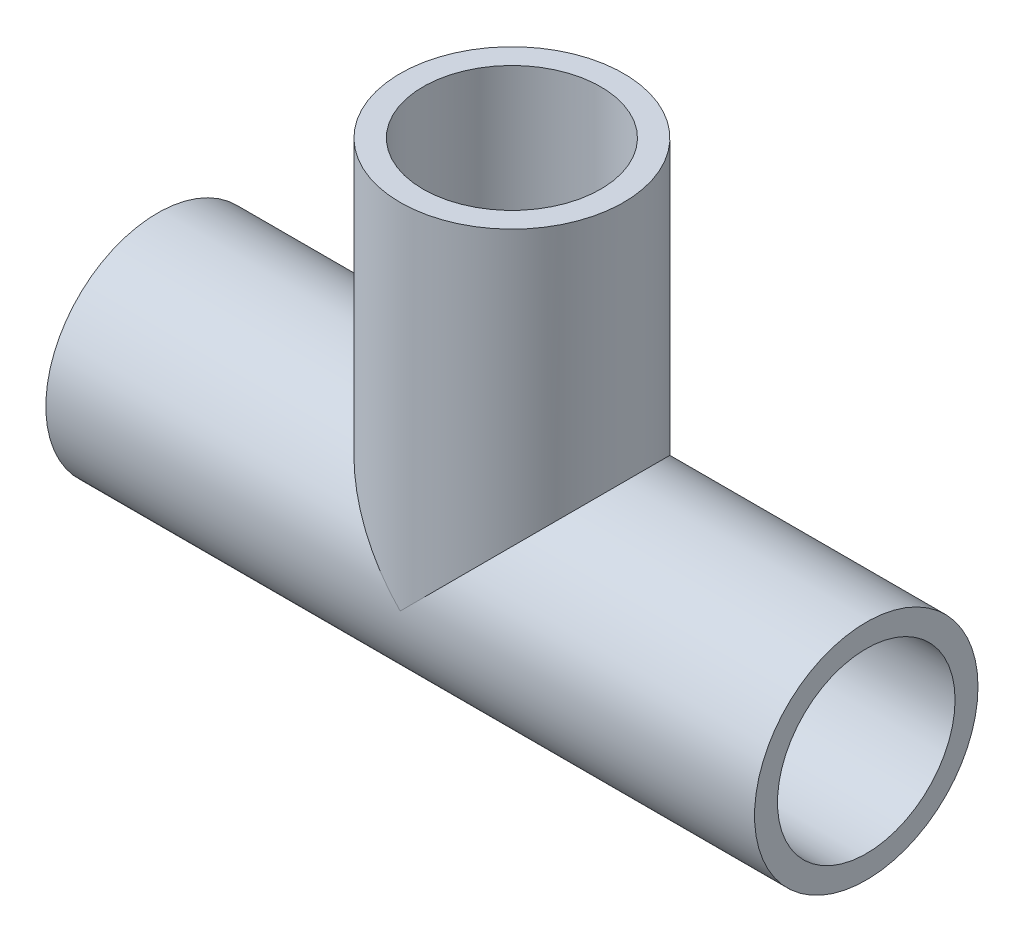
SolidWorks part; units mm, degrees
material "PVC Rígido"
ref_plane "Alzado" through (0, 0, 0) normal (0, 0, 1) x (1, 0, 0)
ref_plane "Planta" through (0, 0, 0) normal (0, 1, 0) x (1, 0, 0)
ref_plane "Vista lateral" through (0, 0, 0) normal (1, 0, 0) x (0, 0, -1)
sketch "Croquis1" plane through (0, 0, 0) normal (1, 0, 0) x (0, 0, -1)
  circle A0 centre (0, 0) radius 10.65
  circle A1 centre (0, 0) radius 13.4
  dimension "D1" = 21.3
  dimension "D2" = 26.8
extrude "Saliente-Extruir1" add sketch "Croquis1" along normal blind 85
sketch "Croquis2" plane through (0, 0, 0) normal (0, 1, 0) x (1, 0, 0)
  line L0 (42.5, 13.4) -> (42.5, -13.4) construction
  line L1 (85, 13.4) -> (0, 13.4) construction
  line L2 (0, -13.4) -> (85, -13.4) construction
  circle A0 centre (42.5, 0) radius 13.4
  circle A1 centre (42.5, 0) radius 10.65
  dimension "D1" = 21.3
extrude "Saliente-Extruir2" add sketch "Croquis2" along normal blind 42.44
sketch "Croquis3" plane through (0, 0, 0) normal (-1, 0, 0) x (0, 0, 1)
  circle A0 centre (0, 0) radius 10.65
  circle A1 centre (0, 0) radius 10.65 construction
extrude "Cortar-Extruir1" cut sketch "Croquis3" against normal blind 84.4974
sketch "Croquis5" plane through (0, 42.44, 0) normal (0, 1, 0) x (1, 0, 0)
  line L0 (31.85, 0) -> (53.15, 0) construction
  circle A0 centre (42.5, 0) radius 10.65 construction
  circle A2 centre (42.5, 0) radius 10.65
  circle A3 centre (42.5, 0) radius 10.65 construction
  point P9 (0, 0)
extrude "Cortar-Extruir2" cut sketch "Croquis5" against normal blind 42.4974
